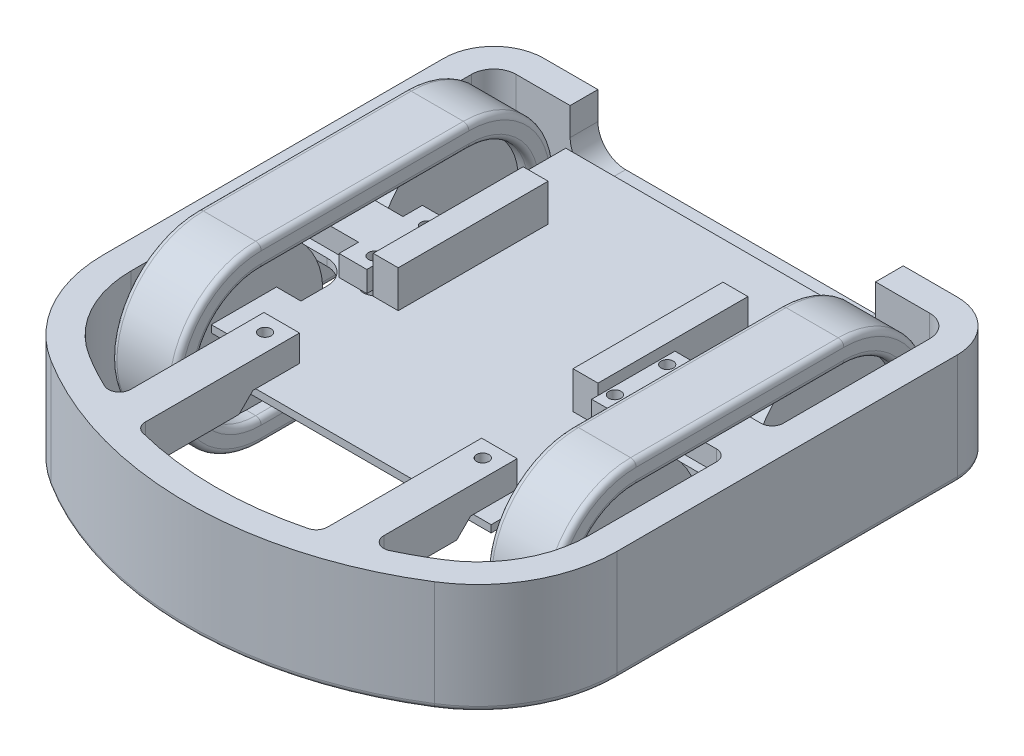
SolidWorks part; units mm, degrees
ref_plane "Front Plane" through (0, 0, 0) normal (0, 0, 1) x (1, 0, 0)
ref_plane "Top Plane" through (0, 0, 0) normal (0, 1, 0) x (1, 0, 0)
ref_plane "Right Plane" through (0, 0, 0) normal (1, 0, 0) x (0, 0, -1)
sketch "Sketch1" plane through (0, 0, 0) normal (0, 1, 0) x (1, 0, 0)
  line L1 (-46.99, 41.5544) -> (46.99, 41.5544)
  line L2 (-46.99, 41.5544) -> (-46.99, -41.5544)
  line L3 (-46.99, -41.5544) -> (46.99, -41.5544)
  line L4 (46.99, 41.5544) -> (46.99, -41.5544)
  line L5 (-46.99, 41.5544) -> (46.99, -41.5544) construction
  line L6 (-46.99, -41.5544) -> (46.99, 41.5544) construction
  point P0 (0, 0)
  dimension "D1" = 93.98
  dimension "D2" = 83.1088
extrude "Boss-Extrude1" add sketch "Sketch1" along normal blind 1.651
sketch "Sketch2" plane through (0, 0, 0) normal (0, 1, 0) x (1, 0, 0)
  line L0 (33.02, 41.5544) -> (33.02, 9.6012)
  line L1 (38.608, 4.0132) -> (46.99, 4.0132)
  line L2 (38.608, -7.493) -> (46.99, -7.493)
  line L3 (46.99, -41.5544) -> (46.99, 41.5544) construction
  line L4 (33.02, -19.0246) -> (38.608, -19.0246)
  line L5 (38.608, -19.0246) -> (38.608, -33.9344)
  line L6 (38.608, -33.9344) -> (33.02, -33.9344)
  line L7 (33.02, -33.9344) -> (33.02, -41.5544)
  line L8 (46.99, -41.5544) -> (46.99, 41.5544) construction
  line L9 (46.99, 41.5544) -> (-46.99, 41.5544) construction
  line L10 (-46.99, -41.5544) -> (46.99, -41.5544) construction
  line L11 (33.02, -19.0246) -> (33.02, -13.081)
  line L12 (33.02, -41.5544) -> (46.99, -41.5544)
  line L13 (46.99, -41.5544) -> (46.99, -7.493)
  line L14 (46.99, 41.5544) -> (33.02, 41.5544)
  line L15 (46.99, 4.0132) -> (46.99, 41.5544)
  line L16 (0, 49.5241) -> (0, -53.2019) construction
  line L17 (-46.99, 4.0132) -> (-46.99, 41.5544)
  line L18 (-46.99, 41.5544) -> (-33.02, 41.5544)
  line L19 (-46.99, -41.5544) -> (-46.99, -7.493)
  line L20 (-33.02, -41.5544) -> (-46.99, -41.5544)
  line L21 (-33.02, -19.0246) -> (-33.02, -13.081)
  line L22 (-33.02, -33.9344) -> (-33.02, -41.5544)
  line L23 (-38.608, -33.9344) -> (-33.02, -33.9344)
  line L24 (-38.608, -19.0246) -> (-38.608, -33.9344)
  line L25 (-33.02, -19.0246) -> (-38.608, -19.0246)
  line L26 (-38.608, -7.493) -> (-46.99, -7.493)
  line L27 (-38.608, 4.0132) -> (-46.99, 4.0132)
  line L28 (-33.02, 41.5544) -> (-33.02, 9.6012)
  arc A0 (38.608, -7.493) -> (33.02, -13.081) centre (38.608, -13.081) ccw
  arc A1 (33.02, 9.6012) -> (38.608, 4.0132) centre (38.608, 9.6012) ccw
  arc A2 (-33.02, 9.6012) -> (-38.608, 4.0132) centre (-38.608, 9.6012) cw
  arc A3 (-38.608, -7.493) -> (-33.02, -13.081) centre (-38.608, -13.081) cw
  point P20 (33.02, -7.493)
  point P38 (-33.02, -7.493)
  dimension "D7" = 5.588
  dimension "D8" = 5.588
  dimension "D1" = 37.5412
  dimension "D2" = 11.5062
  dimension "D3" = 13.97
  dimension "D4" = 14.9098
  dimension "D5" = 7.62
  dimension "D6" = 5.588
extrude "Cut-Extrude3" cut sketch "Sketch2" along normal through all
sketch "Sketch3" plane through (0, 0, 0) normal (0, -1, 0) x (1, 0, 0)
  line L1 (-33.02, -41.5544) -> (33.02, -41.5544)
  line L2 (-33.02, -41.5544) -> (-33.02, 19.0246)
  line L3 (-33.02, 19.0246) -> (33.02, 19.0246)
  line L4 (33.02, -41.5544) -> (33.02, 19.0246)
extrude "Boss-Extrude2" add sketch "Sketch3" along normal blind 19.05
sketch "Sketch4" plane through (0, 1.651, 0) normal (0, 1, 0) x (1, 0, 0)
  line L0 (33.02, -33.9344) -> (33.02, -41.5544) construction
  line L1 (33.02, -13.081) -> (33.02, -19.0246) construction
  line L4 (27.4828, 4.2418) -> (27.4828, -7.7216) construction
  line L5 (46.99, -7.493) -> (46.99, 4.0132) construction
  line L6 (-33.02, -41.5544) -> (33.02, -41.5544) construction
  line L7 (0, 56.6151) -> (0, -59.2562) construction
  circle A0 centre (24.892, -35.3568) radius 1.0795
  circle A4 centre (27.4828, -7.7216) radius 1.0795
  circle A5 centre (27.4828, 4.2418) radius 1.0795
  circle A6 centre (-24.892, -35.3568) radius 1.0795
  circle A7 centre (-27.4828, -7.7216) radius 1.0795
  circle A8 centre (-27.4828, 4.2418) radius 1.0795
  point P4 (46.99, -1.7399)
  point P5 (27.4828, -1.7399)
  dimension "D3" = 2.159
  dimension "D1" = 8.128
  dimension "D2" = 5.5372
  dimension "D4" = 11.9634
  dimension "D5" = 6.1976
extrude "Cut-Extrude4" cut sketch "Sketch4" against normal through all both and the other way through all
sketch "Sketch5" plane through (0, 1.651, 0) normal (0, 1, 0) x (1, 0, 0)
  line L0 (46.99, -7.493) -> (46.99, 4.0132) construction
  line L1 (19.9898, 24.4856) -> (25.7048, 24.4856)
  line L2 (19.9898, 24.4856) -> (19.9898, -9.8044)
  line L3 (19.9898, -9.8044) -> (25.7048, -9.8044)
  line L4 (25.7048, 24.4856) -> (25.7048, -9.8044)
  line L5 (-33.02, -41.5544) -> (33.02, -41.5544) construction
  line L6 (0, 58.6444) -> (0, -57.6745) construction
  line L7 (-25.7048, 24.4856) -> (-25.7048, -9.8044)
  line L8 (-19.9898, -9.8044) -> (-25.7048, -9.8044)
  line L9 (-19.9898, 24.4856) -> (-19.9898, -9.8044)
  line L10 (-19.9898, 24.4856) -> (-25.7048, 24.4856)
  dimension "D1" = 34.29
  dimension "D2" = 21.2852
  dimension "D3" = 5.715
  dimension "D4" = 31.75
extrude "Boss-Extrude3" add sketch "Sketch5" along normal blind 8.509
ref_plane "Plane1" through (42.8752, 0, 0) normal (1, 0, 0) x (0, 0, -1)
sketch "Sketch8" plane through (42.8752, 0, 0) normal (1, 0, 0) x (0, 0, -1)
  line L0 (-45.2343, -5.0038) -> (50.7068, -5.0038) construction
  line L1 (41.5544, 1.651) -> (9.6012, 1.651) construction
  line L2 (-7.493, 0) -> (4.0132, 0) construction
  circle A0 centre (-25.4889, -5.0038) radius 17.526
  circle A1 centre (22.0091, -5.0038) radius 17.526
  point P11 (-1.7399, 0)
  dimension "D2" = 35.052
  dimension "D1" = 6.6548
  dimension "D3" = 47.498
  dimension "D4" = 23.749
extrude "Boss-Extrude4" add sketch "Sketch8" along normal mid plane 7.62 separate body
sketch "Sketch9" plane through (42.8752, 0, 0) normal (1, 0, 0) x (0, 0, -1)
  line L0 (-25.4889, -5.0038) -> (22.0091, -5.0038) construction
  line L1 (-25.4889, 14.8082) -> (22.0091, 14.8082)
  line L2 (-25.4889, -24.8158) -> (22.0091, -24.8158)
  line L3 (-25.4889, 9.7282) -> (22.0091, 9.7282)
  line L4 (-25.4889, -19.7358) -> (22.0091, -19.7358)
  arc A0 (-25.4889, 14.8082) -> (-25.4889, -24.8158) centre (-25.4889, -5.0038) ccw
  arc A1 (22.0091, -24.8158) -> (22.0091, 14.8082) centre (22.0091, -5.0038) ccw
  arc A2 (22.0091, -19.7358) -> (22.0091, 9.7282) centre (22.0091, -5.0038) ccw
  arc A3 (-25.4889, 9.7282) -> (-25.4889, -19.7358) centre (-25.4889, -5.0038) ccw
  point P4 (-1.7399, -5.0038)
  dimension "D1" = 19.812
  dimension "D2" = 5.08
extrude "Boss-Extrude5" add sketch "Sketch9" along normal mid plane 14.478 separate body
fillet "Fillet1" radius 1.27 16 edges at (50.1142, -5.0038, 45.3009) (35.6362, -5.0038, 45.3009) (50.1142, -24.8158, 1.7399) (35.6362, -24.8158, 1.7399) (50.1142, -5.0038, -41.8211) (35.6362, -5.0038, -41.8211) (50.1142, 14.8082, 1.7399) (35.6362, 14.8082, 1.7399) (50.1142, -5.0038, 40.2209) (35.6362, -5.0038, 40.2209) (50.1142, -19.7358, 1.7399) (35.6362, -19.7358, 1.7399) (50.1142, -5.0038, -36.7411) (35.6362, -5.0038, -36.7411) (50.1142, 9.7282, 1.7399) (35.6362, 9.7282, 1.7399)
mirror "Mirror9" about plane through (0, 0, 0) normal (1, 0, 0) of bodies 111 106 107
ref_plane "Plane2" through (0, -5.0038, 0) normal (0, 1, 0) x (1, 0, 0)
sketch "Sketch10" plane through (0, -5.0038, 0) normal (0, 1, 0) x (1, 0, 0)
  line L0 (58.7375, -38.5033) -> (58.7375, 39.37)
  line L1 (52.3875, -50.8) -> (-52.3875, -50.8) construction
  line L2 (52.3875, -38.5033) -> (52.3875, 39.37)
  line L3 (47.3075, 44.45) -> (-47.3075, 44.45)
  line L4 (-52.3875, -38.5033) -> (-52.3875, 39.37)
  line L5 (47.3075, 50.8) -> (-47.3075, 50.8)
  line L6 (-58.7375, -38.5033) -> (-58.7375, 39.37)
  line L7 (52.3875, -44.45) -> (-52.3875, -44.45)
  arc A0 (52.3875, 39.37) -> (47.3075, 44.45) centre (47.3075, 39.37) ccw
  arc A1 (-47.3075, 44.45) -> (-52.3875, 39.37) centre (-47.3075, 39.37) ccw
  arc A2 (40.4812, -60.0225) -> (-40.4812, -60.0225) centre (0, 4.5352) cw
  arc A3 (52.3875, -38.5033) -> (40.4812, -60.0225) centre (26.9875, -38.5033) cw
  arc A4 (-52.3875, -38.5033) -> (-40.4812, -60.0225) centre (-26.9875, -38.5033) ccw
  arc A5 (58.7375, 39.37) -> (47.3075, 50.8) centre (47.3075, 39.37) ccw
  arc A6 (-47.3075, 50.8) -> (-58.7375, 39.37) centre (-47.3075, 39.37) ccw
  arc A7 (-58.7375, -38.5033) -> (-43.8547, -65.4024) centre (-26.9875, -38.5033) ccw
  arc A8 (43.8547, -65.4024) -> (-43.8547, -65.4024) centre (0, 4.5352) cw
  arc A9 (58.7375, -38.5033) -> (43.8547, -65.4024) centre (26.9875, -38.5033) cw
  point P0 (0, 0)
  point P1 (0, 44.45)
  dimension "D3" = 5.08
  dimension "D5" = 76.2
  dimension "D6" = 25.4
  dimension "D1" = 104.775
  dimension "D2" = 44.45
  dimension "D4" = 50.8
  dimension "D7" = 6.35
extrude "Boss-Extrude6" add sketch "Sketch10" along normal blind 12.7 and the other way blind 12.7 separate body
sketch "Sketch11" plane through (0, 0, -50.8) normal (0, 0, -1) x (-1, 0, 0)
  line L0 (-47.3075, 7.6962) -> (47.3075, 7.6962) construction
  line L1 (-34.925, 7.6962) -> (34.925, 7.6962)
  line L2 (-34.925, 7.6962) -> (-34.925, 1.3462)
  line L3 (-28.575, -5.0038) -> (28.575, -5.0038)
  line L4 (34.925, 7.6962) -> (34.925, 1.3462)
  arc A0 (34.925, 1.3462) -> (28.575, -5.0038) centre (28.575, 1.3462) cw
  arc A1 (-28.575, -5.0038) -> (-34.925, 1.3462) centre (-28.575, 1.3462) cw
  point P6 (0, 7.6962)
  point P7 (0, 7.6962)
  dimension "D3" = 6.35
  dimension "D1" = 69.85
  dimension "D2" = 12.7
extrude "Cut-Extrude5" cut sketch "Sketch11" against normal up to next (6.35 mm away)
ref_plane "Plane3" through (0, 1.651, 0) normal (0, 1, 0) x (1, 0, 0)
sketch "Sketch12" plane through (0, 1.651, 0) normal (0, 1, 0) x (1, 0, 0)
  line L0 (0, 54.9132) -> (0, -86.4158) construction
  line L1 (-28.956, -31.5468) -> (-20.828, -31.5468)
  line L2 (-28.956, -31.5468) -> (-28.956, -65.9487)
  line L4 (-20.828, -31.5468) -> (-20.828, -68.763)
  line L5 (20.828, -31.5468) -> (20.828, -68.763)
  line L6 (28.956, -31.5468) -> (28.956, -65.9487)
  line L7 (28.956, -31.5468) -> (20.828, -31.5468)
  circle A1 centre (-24.892, -35.3568) radius 1.397
  circle A2 centre (-24.892, -35.3568) radius 1.0795 construction
  arc A3 (-40.4812, -60.0225) -> (40.4812, -60.0225) centre (0, 4.5352) ccw construction
  arc A4 (-28.956, -65.9487) -> (-20.828, -68.763) centre (0, 4.5352) ccw
  arc A5 (28.956, -65.9487) -> (20.828, -68.763) centre (0, 4.5352) cw
  circle A6 centre (24.892, -35.3568) radius 1.397
  point P5 (-24.892, -31.5468)
  dimension "D2" = 2.794
  dimension "D1" = 8.128
  dimension "D3" = 3.81
extrude "Boss-Extrude7" add sketch "Sketch12" along normal up to surface (6.0452 mm away) and the other way blind 3.175 up to face at (0, 7.6962, -5.4642)
sketch "Sketch16" plane through (0, 0, 0) normal (1, 0, 0) x (0, 0, -1)
  line L0 (-42.1991, 1.6496) -> (-45.3741, -1.5254)
  line L2 (-31.5311, -1.5254) -> (-31.5311, 1.6496)
  line L3 (-31.5311, 1.6496) -> (-42.1991, 1.6496)
  line L4 (-42.1991, -1.5254) -> (-42.1991, 1.6496) construction
  line L5 (-45.3741, -1.5254) -> (-31.5311, -1.5254)
  dimension "D1" = 3.175
  dimension "D2" = 10.668
  dimension "D3" = 31.5311
  dimension "D4" = 1.6496
  dimension "D5" = 45
extrude "Cut-Extrude6" cut sketch "Sketch16" against normal mid plane 63.5
ref_plane "Plane4" through (0, 2.921, 0) normal (0, 1, 0) x (1, 0, 0)
sketch "Sketch18" plane through (0, 2.921, 0) normal (0, 1, 0) x (1, 0, 0)
  line L0 (27.4828, 4.2418) -> (27.4828, -7.7216) construction
  line L1 (-25.7048, 7.7851) -> (-32.0548, 7.7851)
  line L2 (-25.7048, 7.7851) -> (-25.7048, -11.2649)
  line L3 (-25.7048, -11.2649) -> (-32.0548, -11.2649)
  line L4 (-32.0548, 7.7851) -> (-32.0548, 3.3401)
  line L5 (-52.3875, -38.5033) -> (-52.3875, 39.37) construction
  line L6 (-32.0548, -6.8199) -> (-52.3875, -6.8199)
  line L8 (-32.0548, 3.3401) -> (-52.3875, 3.3401)
  line L9 (-52.3875, -6.8199) -> (-52.3875, 3.3401)
  line L10 (-27.4828, 4.2418) -> (-27.4828, -7.7216) construction
  line L11 (-32.0548, -6.8199) -> (-32.0548, -11.2649)
  line L12 (0, 74.689) -> (0, -96.4701) construction
  line L13 (-25.7048, 24.4856) -> (-25.7048, -9.8044) construction
  line L14 (32.0548, -6.8199) -> (32.0548, -11.2649)
  line L15 (52.3875, -6.8199) -> (52.3875, 3.3401)
  line L16 (32.0548, 3.3401) -> (52.3875, 3.3401)
  line L17 (32.0548, -6.8199) -> (52.3875, -6.8199)
  line L18 (32.0548, 7.7851) -> (32.0548, 3.3401)
  line L19 (25.7048, -11.2649) -> (32.0548, -11.2649)
  line L20 (25.7048, 7.7851) -> (25.7048, -11.2649)
  line L21 (25.7048, 7.7851) -> (32.0548, 7.7851)
  circle A0 centre (-27.4828, -7.7216) radius 1.0795 construction
  circle A1 centre (-27.4828, 4.2418) radius 1.0795 construction
  circle A2 centre (-27.4828, -7.7216) radius 1.0795
  circle A3 centre (-27.4828, 4.2418) radius 1.0795
  circle A4 centre (27.4828, 4.2418) radius 1.0795
  circle A5 centre (27.4828, -7.7216) radius 1.0795
  point P4 (-25.7048, -1.7399)
  point P5 (-27.4828, -1.7399)
  point P16 (-52.3875, -1.7399)
  dimension "D1" = 6.35
  dimension "D2" = 19.05
  dimension "D3" = 10.16
  dimension "D4" = 0
extrude "Boss-Extrude9" add sketch "Sketch18" along normal up to surface (4.7752 mm away) up to face at (0, 7.6962, 9.9313)
sketch "Sketch19" plane through (0, 2.921, 0) normal (0, 1, 0) x (1, 0, 0)
  line L5 (-25.7048, -11.2649) -> (-25.7048, 7.7851) construction
  line L6 (-25.7048, -9.5355) -> (-25.7048, -5.9077)
  line L7 (-25.7048, 2.4279) -> (-25.7048, 6.0557)
  line L12 (0, 62.3021) -> (0, -84.394) construction
  line L13 (25.7048, 2.4279) -> (25.7048, 6.0557)
  line L14 (25.7048, -9.5355) -> (25.7048, -5.9077)
  arc A0 (-25.7048, 6.0557) -> (-25.7048, 2.4279) centre (-27.4828, 4.2418) ccw
  arc A1 (-25.7048, -5.9077) -> (-25.7048, -9.5355) centre (-27.4828, -7.7216) ccw
  arc A2 (25.7048, -5.9077) -> (25.7048, -9.5355) centre (27.4828, -7.7216) cw
  arc A3 (25.7048, 6.0557) -> (25.7048, 2.4279) centre (27.4828, 4.2418) cw
  circle A4 centre (27.4828, -7.7216) radius 1.0795 construction
  circle A5 centre (27.4828, 4.2418) radius 1.0795 construction
  circle A6 centre (-27.4828, -7.7216) radius 1.0795 construction
  circle A7 centre (-27.4828, 4.2418) radius 1.0795 construction
  circle A8 centre (27.4828, -7.7216) radius 1.0795
  circle A9 centre (27.4828, 4.2418) radius 1.0795
  circle A10 centre (-27.4828, -7.7216) radius 1.0795
  circle A11 centre (-27.4828, 4.2418) radius 1.0795
  dimension "D1" = 5.08
  dimension "D2" = 5.08
extrude "Boss-Extrude11" add sketch "Sketch19" against normal up to surface (1.27 mm away) up to plane "Plane3"
fillet "Fillet2" radius 2.54 12 edges at (-52.3875, 2.921, 1.7399) (-52.3875, 5.3086, 6.8199) (-52.3875, 5.3086, -3.3401) (52.3875, 5.3086, 6.8199) (52.3875, 5.3086, -3.3401) (28.956, 3.0861, 65.9487) (20.828, 3.0861, 68.763) (-20.828, 3.0861, 68.763) (-28.956, 3.0861, 65.9487) (52.3875, 2.921, 1.7399) (24.9317, -1.524, 67.4706) (-24.9317, -1.524, 67.4706)
fillet "Fillet3" radius 1.27 16 edges at (58.7375, -17.7038, -0.4334) (55.3897, -17.7038, -47.4522) (0, -17.7038, -50.8) (-55.3897, -17.7038, -47.4522) (-58.7375, -17.7038, -0.4334) (-54.7688, -17.7038, 53.8742) (0, -17.7038, 78.0148) (54.7687, -17.7038, 53.8742) (0, -17.7038, 71.6648) (-49.2125, -17.7038, 50.8) (-52.3875, -17.7038, -0.4334) (-50.8996, -17.7038, -42.9621) (0, -17.7038, -44.45) (50.8996, -17.7038, -42.9621) (52.3875, -17.7038, -0.4334) (49.2125, -17.7038, 50.8)
other "Save Bodies1"
other "Save Bodies2"
sketch "Sketch20" plane through (0, 7.6962, 0) normal (0, 1, 0) x (1, 0, 0)
  circle A0 centre (-27.4828, 4.2418) radius 1.397
  circle A1 centre (-27.4828, -7.7216) radius 1.397
  circle A2 centre (27.4828, -7.7216) radius 1.397
  circle A3 centre (27.4828, 4.2418) radius 1.397
  dimension "D1" = 2.794
  dimension "D2" = 2.794
  dimension "D3" = 2.794
  dimension "D4" = 2.794
extrude "Cut-Extrude7" cut sketch "Sketch20" against normal up to next
other "Save Bodies3"
equation "\"D4@Sketch8\"=\"D3@Sketch8\"/2"
equation "\"D2@Sketch19\"=\"D1@Sketch19\""
equation "\"D2@Sketch20\"=\"D1@Sketch20\""
equation "\"D3@Sketch20\"=\"D1@Sketch20\""
equation "\"D4@Sketch20\"=\"D1@Sketch20\""
